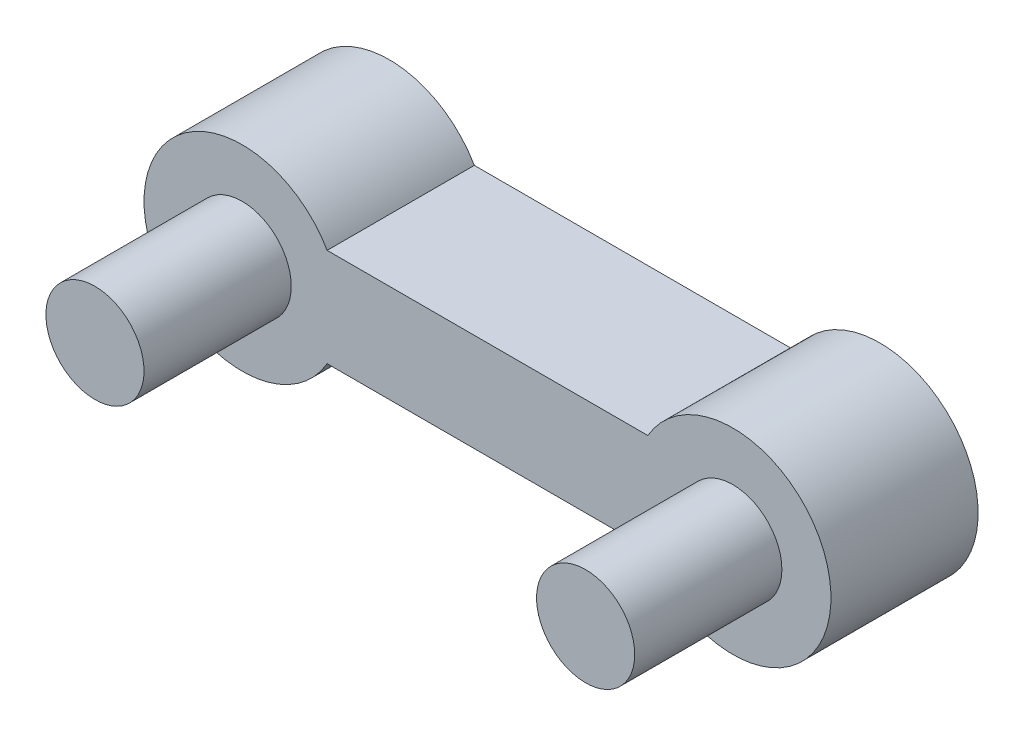
SolidWorks part; units mm, degrees
ref_plane "Спереди" through (0, 0, 0) normal (0, 0, 1) x (1, 0, 0)
ref_plane "Сверху" through (0, 0, 0) normal (0, 1, 0) x (1, 0, 0)
ref_plane "Справа" through (0, 0, 0) normal (1, 0, 0) x (0, 0, -1)
other "Configuration Table"
sketch "Sketch2" plane through (0, 0, 0) normal (0, 0, 1) x (1, 0, 0)
  line L1 (-36.505, 13.8003) -> (-29.9691, 13.8003)
  line L5 (-36.505, 11.8003) -> (-29.9691, 11.8003)
  line L7 (-13.5959, 12.8003) -> (-45.3291, 12.8003) construction
  arc A0 (-36.505, 13.8003) -> (-36.505, 11.8003) centre (-38.2371, 12.8003) ccw
  arc A2 (-29.9691, 13.8003) -> (-29.9691, 11.8003) centre (-28.2371, 12.8003) cw
  dimension "D3" = 4
  dimension "D1" = 2
  dimension "D2" = 10
extrude "Boss-Extrude1" add sketch "Sketch2" along normal blind 3 contours L1 A0 | A2 L1 A0 | A2 L1 | A0 | A2 region at (-33.2371, 12.8003, 0)
ref_plane "Plane1" through (0, 0, 3) normal (0, 0, 1) x (1, 0, 0)
sketch "Sketch3" plane through (0, 0, 3) normal (0, 0, 1) x (1, 0, 0)
  circle A0 centre (-38.2371, 12.8003) radius 1
  circle A1 centre (-28.2371, 12.8003) radius 1
  dimension "D1" = 2
extrude "Boss-Extrude2" add sketch "Sketch3" along normal blind 3 contours A1 | A0 region at (-38.2371, 12.8003, 3) region at (-28.2371, 12.8003, 3)
equation "\"R small\"= 2"
equation "\"R big\"= 4"
equation "\"width\"= 0.6"
equation "\"border width\"= 1"
equation "\"D3@Sketch2\"=\"R big\""
equation "\"D1@Sketch2\"=\"R small\""
equation "\"D1@Sketch3\"=\"R small\""
